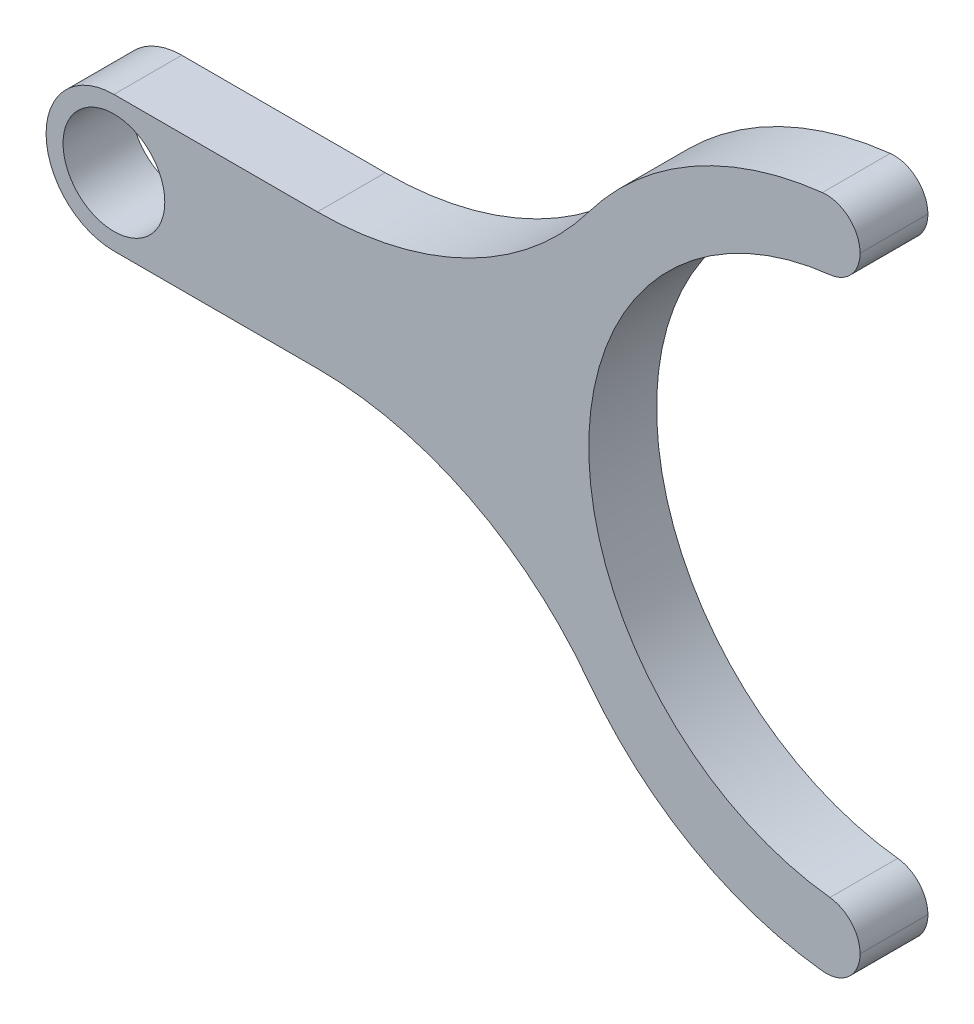
SolidWorks part; units mm, degrees
ref_plane "Front Plane" through (0, 0, 0) normal (0, 0, 1) x (1, 0, 0)
ref_plane "Top Plane" through (0, 0, 0) normal (0, 1, 0) x (1, 0, 0)
ref_plane "Right Plane" through (0, 0, 0) normal (1, 0, 0) x (0, 0, -1)
sketch "Sketch1" plane through (0, 0, 0) normal (0, 0, 1) x (1, 0, 0)
  line L0 (-319.8772, 0) -> (15673.9835, 0) construction
  line L1 (0, -319.8772) -> (0, 15673.9835) construction
  line L2 (40, -50) -> (40, -40)
  line L7 (-40, 10) -> (-70, 10)
  line L9 (-40, -10) -> (-70, -10)
  line L11 (40, 40) -> (40, 50)
  arc A0 (40, 40) -> (40, -40) centre (40, 0) ccw
  arc A1 (0, -30) -> (40, -50) centre (40, 0) ccw
  arc A2 (-40, 10) -> (0, 30) centre (-40, 60) ccw
  arc A3 (-40, -10) -> (0, -30) centre (-40, -60) cw
  arc A4 (-70, 10) -> (-70, -10) centre (-70, 0) ccw
  arc A5 (40, 50) -> (0, 30) centre (40, 0) ccw
  circle A6 centre (-70, 0) radius 7.5
  point P12 (-40, 0)
  point P22 (40, 0)
  dimension "D1" = 80
  dimension "D2" = 100
  dimension "D3" = 100
  dimension "D4" = 60
  dimension "D5" = 10
  dimension "D7" = 15
  dimension "D6" = 110
extrude "Boss-Extrude1" add sketch "Sketch1" along normal mid plane 10
fillet "Fillet2" radius 5 4 edges at (40, -50, 0) (40, -40, 0) (40, 50, 0) (40, 40, 0)
